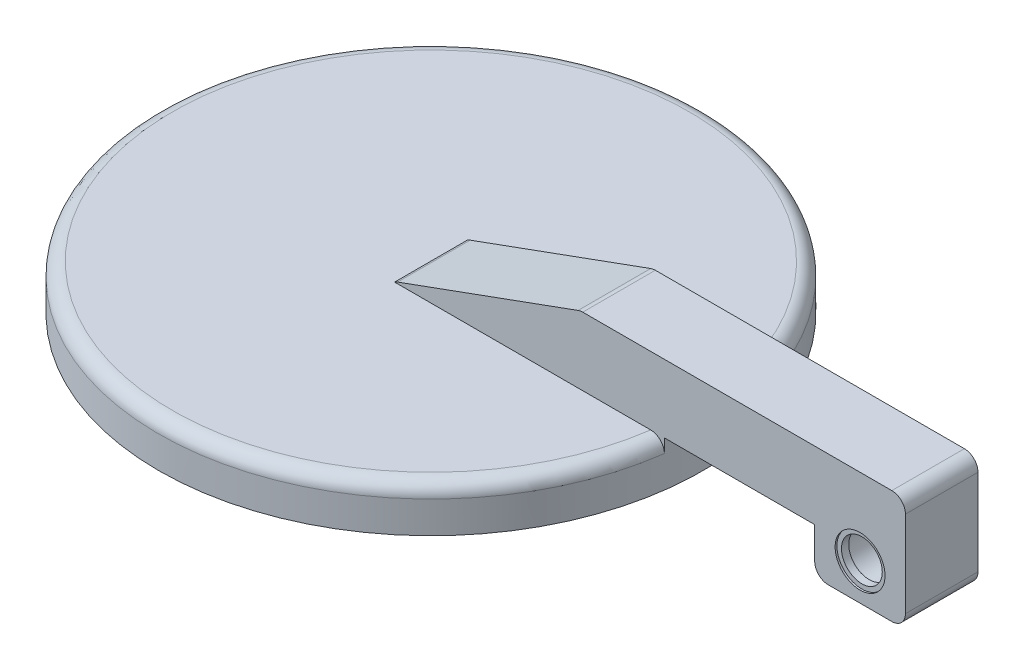
SolidWorks part; units mm, degrees
ref_plane "Front Plane" through (0, 0, 0) normal (0, 0, 1) x (1, 0, 0)
ref_plane "Top Plane" through (0, 0, 0) normal (0, 1, 0) x (1, 0, 0)
ref_plane "Right Plane" through (0, 0, 0) normal (1, 0, 0) x (0, 0, -1)
sketch "Sketch2" plane through (0, 0, 0) normal (0, 0, 1) x (1, 0, 0)
  line L7 (0, 0) -> (30, 0)
  line L8 (0, 0) -> (0, 5)
  line L9 (0, 5) -> (30, 5)
  line L10 (30, 0) -> (30, 5)
  dimension "D1" = 5
  dimension "D2" = 30
revolve "Revolve1" add sketch "Sketch2" angle 360 about L8
sketch "Sketch3" plane through (0, 5, 0) normal (0, 1, 0) x (1, 0, 0)
  line L0 (0, -10) -> (0, 10) construction
  line L1 (0, 10) -> (35, 10)
  line L2 (35, 10) -> (35, 6)
  line L3 (35, 6) -> (0, 6)
  line L4 (0, 10) -> (0, 6)
  line L5 (0, -10) -> (35, -10)
  line L6 (35, -10) -> (35, -6)
  line L7 (35, -6) -> (0, -6)
  line L8 (0, -6) -> (0, -10)
  line L9 (0, 4) -> (0, -4)
  line L10 (0, 4) -> (56.3, 4)
  line L11 (0, -4) -> (56.3, -4)
  line L12 (56.3, -4) -> (56.3, 4)
  point P4 (0, 0)
  point P13 (0, 0)
  circle M1 centre (0, 0) radius 30
  dimension "D1" = 20
  dimension "D2" = 35
  dimension "D3" = 4
  dimension "0.7" = 8
  dimension "D5" = 56.3
extrude "Boss-Extrude1" add sketch "Sketch3" along normal blind 7.5 contours L9 L11 L10 M1 | L11 L12 L10 M1 region at (14.9555, 5, 0) region at (43.1053, 5, 0)
sketch "Sketch4" plane through (0, 0, 0) normal (0, 0, 1) x (1, 0, 0)
  line L5 (35, 8.75) -> (37.8, 8.75) construction
  line L7 (56.3, 8.75) -> (37.8, 8.75) construction
  line L8 (56.3, 12.5) -> (56.3, 5) construction
  line L10 (-0.1339, 5) -> (20.4721, 12.5)
  line L11 (29.7321, 5) -> (-30, 5) construction
  line L12 (0, 12.5) -> (56.3, 12.5) construction
  line L13 (0, 5) -> (29.7321, 5) construction
  line L14 (20.4721, 12.5) -> (0, 12.5)
  line L15 (0, 12.5) -> (-0.1339, 5)
  circle A0 centre (37.8, 8.75) radius 2
  dimension "D3" = 4
  dimension "D1" = 20
  dimension "D2" = 18.5
extrude "Cut-Extrude1" cut sketch "Sketch4" against normal mid plane 30 contours L14 L15 L10
sketch "Sketch6" plane through (0, 5, 0) normal (0, -1, 0) x (1, 0, 0)
  line L6 (56.3, 4) -> (46.3, 4)
  line L7 (56.3, 4) -> (56.3, -4) construction
  line L8 (29.7321, 4) -> (56.3, 4) construction
  line L9 (46.3, 4) -> (46.3, -4)
  line L10 (29.7321, -4) -> (56.3, -4) construction
  line L11 (46.3, -4) -> (56.3, -4)
  line L12 (56.3, -4) -> (56.3, 4)
  dimension "D1" = 10
extrude "Boss-Extrude2" add sketch "Sketch6" along normal blind 5
sketch "Sketch7" plane through (0, 0, 4) normal (0, 0, 1) x (1, 0, 0)
  line L0 (51.3, 4) -> (51.3, 0) construction
  line L2 (56.3, 0) -> (46.3, 0) construction
  circle A0 centre (51.3, 4) radius 2.75
  dimension "D2" = 5.5
  dimension "D1" = 4
extrude "Cut-Extrude2" cut sketch "Sketch7" against normal blind 10
fillet "Fillet2" radius 1.5 6 edges at (46.3, 0, 0) (56.3, 0, 0) (56.3, 12.5, 0) (20.4721, 12.5, 0) (0, 5.0487, 0) (-30, 5, 0)
sketch "Sketch9" plane through (0, 0, -4) normal (0, 0, -1) x (-1, 0, 0)
  circle A0 centre (-51.3, 4) radius 3
  circle A1 centre (-51.3, 4) radius 4
  dimension "D1" = 6
  dimension "D2" = 8
sketch "Sketch10" plane through (0, 0, 4) normal (0, 0, 1) x (1, 0, 0)
  circle A0 centre (51.3, 4) radius 3
  circle A1 centre (51.3, 4) radius 2.25
  dimension "D1" = 6
  dimension "D2" = 4.5
extrude "Boss-Extrude4" add sketch "Sketch10" along normal blind 0.8 from offset 1 offset against normal yes
